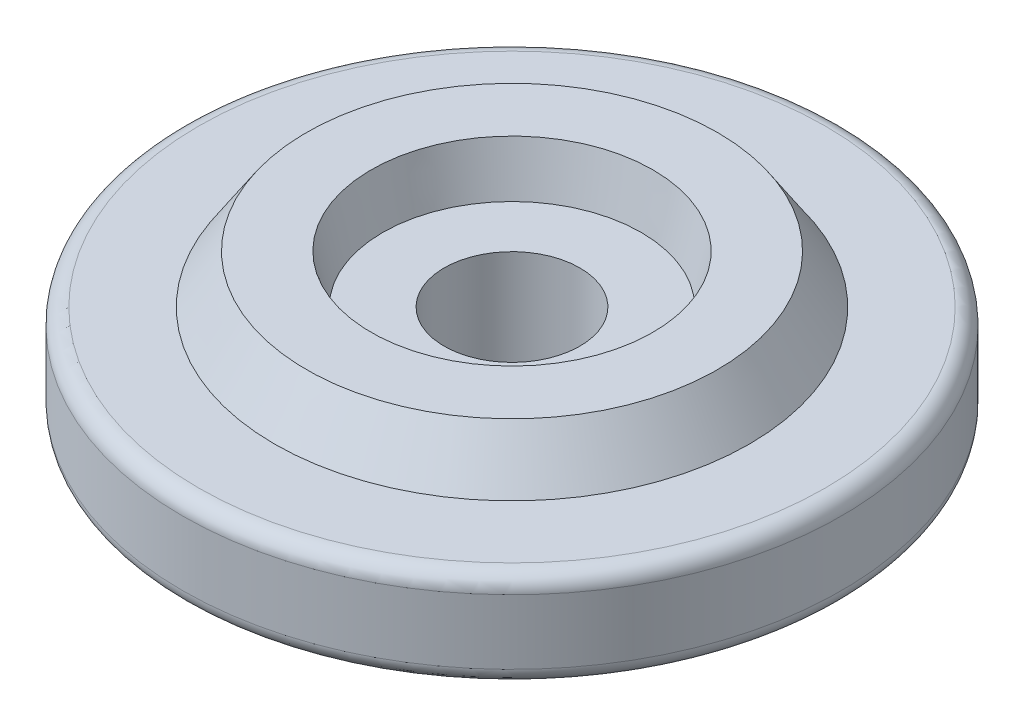
SolidWorks part; units mm, degrees
ref_plane "Front Plane" through (0, 0, 0) normal (0, 0, 1) x (1, 0, 0)
ref_plane "Top Plane" through (0, 0, 0) normal (0, 1, 0) x (1, 0, 0)
ref_plane "Right Plane" through (0, 0, 0) normal (1, 0, 0) x (0, 0, -1)
sketch "Sketch1" plane through (0, 0, 0) normal (0, 0, 1) x (1, 0, 0)
  line L0 (2.1, 0) -> (2.1, 3)
  line L1 (2.1, 3) -> (4, 3)
  line L2 (4, 3) -> (4.3594, 4.5)
  line L3 (4.3594, 4.5) -> (6.3594, 4.5)
  line L4 (6.3594, 4.5) -> (7.348, 3)
  line L5 (7.348, 3) -> (9.7, 3)
  line L6 (10.2, 2.5) -> (10.2, 0.5)
  line L7 (9.7, 0) -> (2.1, 0)
  line L8 (0, 0) -> (0, 4.2807) construction
  arc A0 (10.2, 0.5) -> (9.7, 0) centre (9.7, 0.5) cw
  arc A1 (9.7, 3) -> (10.2, 2.5) centre (9.7, 2.5) cw
  point P19 (10.2, 0)
  point P22 (10.2, 3)
  dimension "D7" = 0.5
  dimension "D1" = 10.2
  dimension "D2" = 2.1
  dimension "D3" = 4
  dimension "D4" = 3
  dimension "D5" = 4.5
  dimension "D6" = 2
revolve "Revolve1" add sketch "Sketch1" angle 360 about L8
